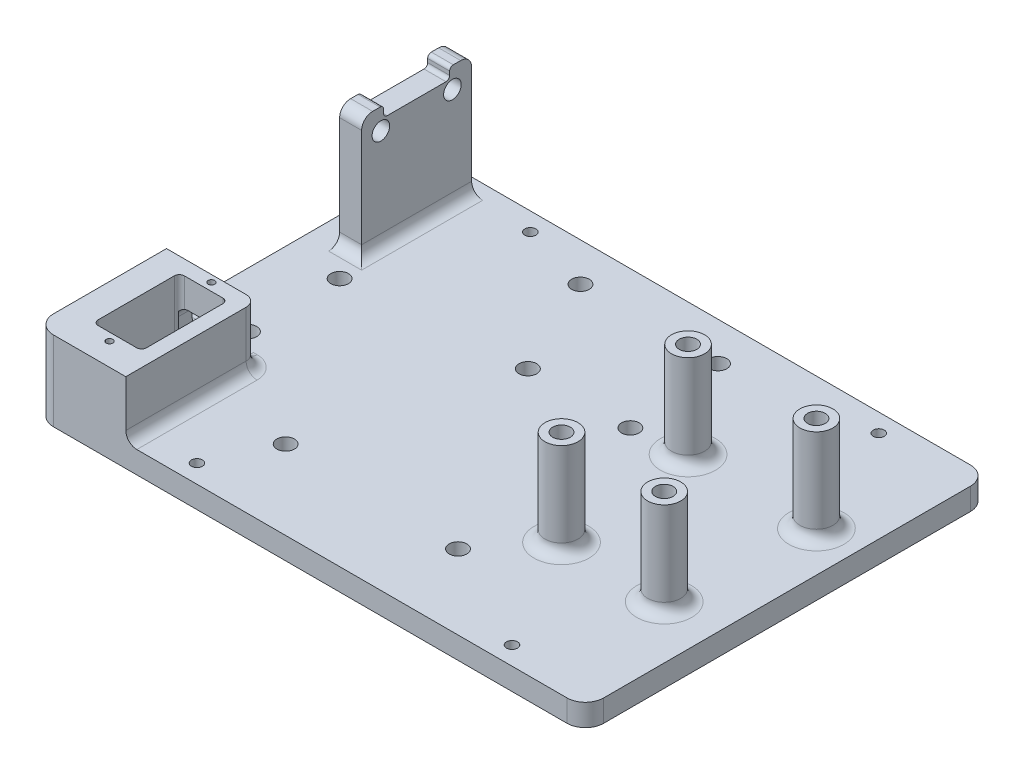
SolidWorks part; units mm, degrees
ref_plane "Front Plane" through (0, 0, 0) normal (0, 0, 1) x (1, 0, 0)
ref_plane "Top Plane" through (0, 0, 0) normal (0, 1, 0) x (1, 0, 0)
ref_plane "Right Plane" through (0, 0, 0) normal (1, 0, 0) x (0, 0, -1)
sketch "Sketch1" plane through (0, 0, 0) normal (0, 1, 0) x (1, 0, 0)
  line L1 (0, 0) -> (150, 0)
  line L2 (0, 0) -> (0, 110)
  line L3 (0, 110) -> (150, 110)
  line L4 (150, 0) -> (150, 110)
  dimension "D1" = 150
  dimension "D2" = 110
extrude "Boss-Extrude1" add sketch "Sketch1" along normal blind 6
hole_wizard "#12 (0.189) Diameter Hole1" positions "Sketch2" profile "Sketch3" hole size "#12" standard "ANSI Inch" end condition up to next
sketch "Sketch2" plane through (0, 6, 0) normal (0, 1, 0) x (1, 0, 0)
  point P0 (89.88, 72.39)
  point P3 (61.94, 72.39)
  point P6 (46.7, 21.59)
  point P9 (94.96, 20.32)
  point P24 (49.16, 99.5)
  point P27 (86.66, 99.5)
  point P30 (15, 68)
  point P33 (15, 43)
sketch "Sketch3" plane through (89.88, 6, -72.39) normal (1, 0, 0) x (0, 0, 1)
  line L0 (0, 0) -> (0, 6)
  line L1 (0, 6) -> (2.4003, 6)
  line L2 (2.4003, 6) -> (2.4003, 0)
  line L5 (2.4003, 0) -> (0, 0)
  line L11 (0, -6.35) -> (0, 107.95) construction
  dimension "Thru Hole Dia." = 4.8006
  dimension "Thru Hole Depth" = 6
sketch "Sketch4" plane through (0, 6, 0) normal (0, 1, 0) x (1, 0, 0)
  line L0 (150, 110) -> (0, 110) construction
  line L1 (7, 106) -> (13, 106)
  line L2 (7, 106) -> (7, 76)
  line L3 (7, 76) -> (13, 76)
  line L4 (13, 106) -> (13, 76)
  line L5 (0, 110) -> (0, 0) construction
  dimension "D1" = 30
  dimension "D2" = 6
  dimension "D3" = 4
  dimension "D4" = 7
extrude "Boss-Extrude2" add sketch "Sketch4" along normal blind 30
ref_plane "Plane1" through (0, 0, -91) normal (0, 0, -1) x (-1, 0, 0)
hole_wizard "#12 (0.189) Diameter Hole2" positions "Sketch5" profile "Sketch6" hole size "#12" standard "ANSI Inch" end condition up to next
sketch "Sketch5" plane through (7, 0, 0) normal (-1, 0, 0) x (0, 0, 1)
  point P0 (-81.25, 33.27)
  point P3 (-100.75, 33.27)
sketch "Sketch6" plane through (7, 33.27, -81.25) normal (0, 1, 0) x (0, 0, 1)
  line L0 (0, 0) -> (0, 6)
  line L1 (0, 6) -> (2.4003, 6)
  line L2 (2.4003, 6) -> (2.4003, 0)
  line L5 (2.4003, 0) -> (0, 0)
  line L11 (0, -6.35) -> (0, 107.95) construction
  dimension "Thru Hole Dia." = 4.8006
  dimension "Thru Hole Depth" = 6
sketch "Sketch7" plane through (0, 36, 0) normal (0, 1, 0) x (1, 0, 0)
  line L0 (13, 76) -> (13, 106) construction
  line L1 (7, 106) -> (13, 106)
  line L2 (7, 106) -> (7, 100)
  line L3 (7, 100) -> (13, 100)
  line L4 (13, 106) -> (13, 100)
  line L6 (7, 76) -> (13, 76)
  line L7 (7, 76) -> (7, 82)
  line L8 (7, 82) -> (13, 82)
  line L9 (13, 76) -> (13, 82)
  dimension "D1" = 6
  dimension "D2" = 6
extrude "Boss-Extrude3" add sketch "Sketch7" along normal blind 3
sketch "Sketch9" plane through (0, 6, 0) normal (0, 1, 0) x (1, 0, 0)
  line L0 (20.2, 9.65) -> (20.2, 30.45) construction
  line L1 (8.85, 8.8) -> (19.35, 8.8) construction
  line L2 (8, 30.45) -> (8, 9.65) construction
  line L3 (19.35, 31.3) -> (8.85, 31.3) construction
  line L4 (20.2, 9.65) -> (20.2, 30.45) construction
  line L5 (8.85, 8.8) -> (19.35, 8.8) construction
  line L6 (8, 30.45) -> (8, 9.65) construction
  line L7 (19.35, 31.3) -> (8.85, 31.3) construction
  line L8 (20.7, 9.65) -> (20.7, 30.45)
  line L9 (19.35, 31.8) -> (8.85, 31.8)
  line L10 (7.5, 30.45) -> (7.5, 9.65)
  line L11 (8.85, 8.3) -> (19.35, 8.3)
  line L13 (0, 0) -> (24.7, 0)
  line L14 (0, 0) -> (0, 35.8)
  line L15 (0, 35.8) -> (24.7, 35.8)
  line L16 (24.7, 0) -> (24.7, 35.8)
  arc A0 (20.2, 30.45) -> (19.35, 31.3) centre (19.35, 30.45) ccw construction
  arc A1 (19.35, 8.8) -> (20.2, 9.65) centre (19.35, 9.65) ccw construction
  arc A2 (8, 9.65) -> (8.85, 8.8) centre (8.85, 9.65) ccw construction
  arc A3 (8.85, 31.3) -> (8, 30.45) centre (8.85, 30.45) ccw construction
  arc A4 (20.2, 30.45) -> (19.35, 31.3) centre (19.35, 30.45) ccw construction
  arc A5 (19.35, 8.8) -> (20.2, 9.65) centre (19.35, 9.65) ccw construction
  arc A6 (8, 9.65) -> (8.85, 8.8) centre (8.85, 9.65) ccw construction
  arc A7 (8.85, 31.3) -> (8, 30.45) centre (8.85, 30.45) ccw construction
  arc A8 (20.7, 30.45) -> (19.35, 31.8) centre (19.35, 30.45) ccw
  arc A9 (8.85, 31.8) -> (7.5, 30.45) centre (8.85, 30.45) ccw
  arc A10 (7.5, 9.65) -> (8.85, 8.3) centre (8.85, 9.65) ccw
  arc A11 (19.35, 8.3) -> (20.7, 9.65) centre (19.35, 9.65) ccw
  dimension "D2" = 4
  dimension "D3" = 4
  dimension "D1" = 0.5
extrude "Boss-Extrude4" add sketch "Sketch9" along normal blind 15.7
sketch "Sketch10" plane through (0, 0, -35.8) normal (0, 0, -1) x (-1, 0, 0)
  line L0 (-7, 39) -> (-7, 6) construction
  line L1 (-20.7, 6) -> (-7, 6)
  line L2 (-20.7, 6) -> (-20.7, 14)
  line L3 (-20.7, 14) -> (-7, 14)
  line L4 (-7, 6) -> (-7, 14)
  dimension "D1" = 8
extrude "Cut-Extrude1" cut sketch "Sketch10" against normal up to surface (4.5 mm away)
sketch "Sketch11" plane through (0, 6, 0) normal (0, 1, 0) x (1, 0, 0)
  arc A0 (108.75, 36) -> (106.25, 36) centre (107.5, 36) ccw construction
  arc A1 (136.75, 36) -> (134.25, 36) centre (135.5, 36) ccw construction
  arc A2 (140.25, 74) -> (137.75, 74) centre (139, 74) ccw construction
  arc A3 (105.25, 74) -> (102.75, 74) centre (104, 74) ccw construction
  arc A4 (108.75, 36) -> (106.25, 36) centre (107.5, 36) ccw construction
  arc A5 (136.75, 36) -> (134.25, 36) centre (135.5, 36) ccw construction
  arc A6 (140.25, 74) -> (137.75, 74) centre (139, 74) ccw construction
  arc A7 (105.25, 74) -> (102.75, 74) centre (104, 74) ccw construction
  circle A8 centre (104, 74) radius 4.5
  circle A9 centre (139, 74) radius 4.5
  circle A10 centre (107.5, 36) radius 4.5
  circle A11 centre (135.5, 36) radius 4.5
  dimension "D1" = 9
extrude "Boss-Extrude5" add sketch "Sketch11" along normal blind 26
hole_wizard "#12 (0.189) Diameter Hole3" positions "Sketch12" profile "Sketch13" hole size "#12" standard "ANSI Inch" end condition up to next
sketch "Sketch12" plane through (0, 32, 0) normal (0, 1, 0) x (1, 0, 0)
  point P0 (104, 74)
  point P3 (139, 74)
  point P6 (107.5, 36)
  point P9 (135.5, 36)
sketch "Sketch13" plane through (104, 32, -74) normal (1, 0, 0) x (0, 0, 1)
  line L0 (0, 0) -> (0, 32)
  line L1 (0, 32) -> (2.4003, 32)
  line L2 (2.4003, 32) -> (2.4003, 0)
  line L5 (2.4003, 0) -> (0, 0)
  line L11 (0, -6.35) -> (0, 107.95) construction
  dimension "Thru Hole Dia." = 4.8006
  dimension "Thru Hole Depth" = 32
fillet "Fillet3" radius 5 4 edges at (150, 3, -110) (150, 3, 0) (0, 10.85, 0) (0, 3, -110)
fillet "Fillet4" radius 3 14 edges at (107.5, 6, -40.5) (10, 39, -76) (10, 39, -106) (10, 6, -76) (13, 6, -91) (20.7, 14, -33.55) (7, 14, -33.55) (24.7, 13.85, -35.8) (22.7, 6, -35.8) (3.5, 6, -35.8) (24.7, 6, -17.9) (104, 6, -78.5) (139, 6, -78.5) (135.5, 6, -40.5)
fillet "Fillet5" radius 1 4 edges at (10, 36, -100) (10, 39, -100) (10, 39, -82) (10, 36, -82)
hole_wizard "Ø3.0mm Dowel Hole1" positions "Sketch14" profile "Sketch15" hole size "Ø3.0" standard "ANSI Metric" end condition up to next
sketch "Sketch14" plane through (0, 6, 0) normal (0, 1, 0) x (1, 0, 0)
  line L0 (145, 110) -> (5, 110) construction
  line L1 (150, 5) -> (150, 105) construction
  line L3 (27.7, 0) -> (145, 0) construction
  line L4 (0, 105) -> (0, 38.8) construction
  line L6 (34.1, 0) -> (34.1, 40.2) construction
  point P0 (30, 105)
  point P2 (39.1, 5)
  point P4 (125, 5)
  point P6 (125, 105)
  dimension "D1" = 5
  dimension "D2" = 25
  dimension "D3" = 5
  dimension "D4" = 5
  dimension "D5" = 30
sketch "Sketch15" plane through (30, 6, -105) normal (1, 0, 0) x (0, 0, 1)
  line L0 (0, 0) -> (0, 6)
  line L1 (0, 6) -> (1.5, 6)
  line L2 (1.5, 6) -> (1.5, 0)
  line L5 (1.5, 0) -> (0, 0)
  line L11 (0, -6.35) -> (0, 107.95) construction
  dimension "Thru Hole Dia." = 3
  dimension "Thru Hole Depth" = 6
sketch "Sketch16" plane through (0, 21.7, 0) normal (0, 1, 0) x (1, 0, 0)
  circle A0 centre (14.1, 6.15) radius 0.9
  circle A1 centre (14.1, 33.95) radius 0.9
  dimension "D1" = 1.8
  dimension "D2" = 1.8
extrude "Cut-Extrude2" cut sketch "Sketch16" against normal blind 5
